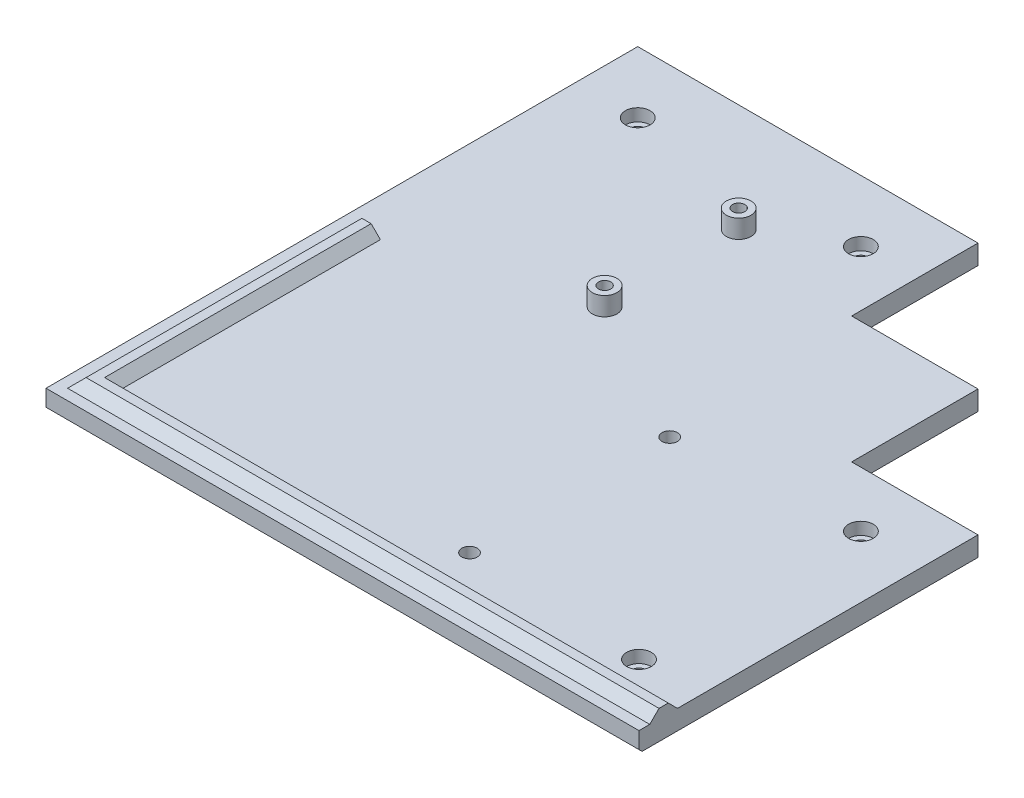
SolidWorks part; units mm, degrees
ref_plane "Front Plane" through (0, 0, 0) normal (0, 0, 1) x (1, 0, 0)
ref_plane "Top Plane" through (0, 0, 0) normal (0, 1, 0) x (1, 0, 0)
ref_plane "Right Plane" through (0, 0, 0) normal (1, 0, 0) x (0, 0, -1)
sketch "Sketch1" plane through (0, 0, 0) normal (0, 1, 0) x (1, 0, 0)
  line L1 (-96.2, 96) -> (96.2, 96)
  line L2 (-96.2, 96) -> (-96.2, -96)
  line L3 (-96.2, -96) -> (96.2, -96)
  line L4 (96.2, 96) -> (96.2, -96)
  line L5 (-96.2, 96) -> (96.2, -96) construction
  line L6 (-96.2, -96) -> (96.2, 96) construction
  point P0 (0, 0)
  dimension "D1" = 192
  dimension "D2" = 192.4
extrude "Boss-Extrude1" add sketch "Sketch1" along normal blind 6.35
sketch "Sketch2" plane through (0, 6.35, 0) normal (0, 1, 0) x (1, 0, 0)
  line L1 (-96.2, 96) -> (-55.2, 96)
  line L2 (-96.2, 96) -> (-96.2, 55)
  line L3 (-96.2, 55) -> (-55.2, 55) construction
  line L4 (-55.2, 96) -> (-55.2, 55) construction
  line L5 (-96.2, 55) -> (-55.2, 55)
  line L6 (-96.2, 55) -> (-96.2, 14)
  line L7 (-96.2, 14) -> (-55.2, 14)
  line L8 (-55.2, 55) -> (-55.2, 14)
  line L9 (-55.2, 96) -> (-14.2, 96)
  line L10 (-55.2, 96) -> (-55.2, 55)
  line L11 (-55.2, 55) -> (-14.2, 55)
  line L12 (-14.2, 96) -> (-14.2, 55)
  line M14 (96.2, 96) -> (-96.2, 96)
  line M15 (-96.2, 96) -> (-96.2, -96)
  dimension "D1" = 41
extrude "Cut-Extrude1" cut sketch "Sketch2" against normal up to next contours L8 L5 L7 M15 | L10 L5 M14 M15 | L12 L10 L11 M14 region at (-75.7, 6.35, -75.5) region at (-34.7, 6.35, -75.5) region at (-75.7, 6.35, -34.5)
sketch "Sketch3" plane through (0, 6.35, 0) normal (0, 1, 0) x (1, 0, 0)
  line L0 (-96.2, 76) -> (96.2, 76) construction
  line L1 (-96.2, 96) -> (-56.2, 96) construction
  line L2 (-96.2, 96) -> (-96.2, -96) construction
  line L3 (-96.2, -96) -> (-56.2, -96) construction
  line L4 (96.2, 96) -> (-96.2, 96)
  line L5 (96.2, -96) -> (96.2, 96)
  line L6 (-96.2, -96) -> (96.2, -96)
  line L7 (-96.2, 96) -> (-96.2, -96)
  line L8 (96.2, 96) -> (-96.2, 96) construction
  line L9 (96.2, -96) -> (96.2, 96) construction
  line L10 (-96.2, -96) -> (96.2, -96) construction
  line L11 (-96.2, 96) -> (-96.2, -96) construction
  line L12 (-56.2, 96) -> (-56.2, -96) construction
  line L13 (-96.2, 96) -> (96.2, 96) construction
  line L14 (-96.2, 96) -> (-96.2, 56) construction
  line L15 (-96.2, 56) -> (96.2, 56) construction
  line L16 (96.2, 96) -> (96.2, 56) construction
  line L17 (-76.2, 96) -> (-76.2, -96) construction
  point P20 (-76.2, -4)
  point P22 (-76.2, -76)
  point P24 (3.8, 76)
  point P26 (76.2, 76)
  dimension "D2" = 40
  dimension "D3" = 40
  dimension "D4" = 20
  dimension "D5" = 60
  dimension "D6" = 60
  dimension "D7" = 20
  dimension "D8" = 20
  dimension "D1" = 0
hole_wizard "CBORE for M4 SHCS1" positions "Sketch3" profile "Sketch4" counterbore size "M4" standard "ANSI Metric" end condition up to next
sketch "Sketch4" plane through (76.2, 6.35, -76) normal (1, 0, 0) x (0, 0, 1)
  line L0 (0, 0) -> (0, 6.35)
  line L1 (0, 6.35) -> (2.25, 6.35)
  line L3 (2.25, 6.35) -> (2.25, 4)
  line L4 (2.25, 4) -> (4, 4)
  line L5 (4, 4) -> (4, 0)
  line L7 (4, 0) -> (0, 0)
  line L11 (0, -6.35) -> (0, 107.95) construction
  dimension "Thru Hole Dia." = 4.5
  dimension "Thru Hole Depth" = 6.35
  dimension "C'Bore Dia." = 8
  dimension "C'Bore Depth" = 4
mirror "Mirror1" [suppressed] of bodies 105
delete or keep bodies "Body-Delete/Keep 1" [suppressed] type delete bodies bodies 105
mirror "Mirror2" [suppressed] of bodies 108
delete or keep bodies "Body-Delete/Keep 2" [suppressed] type delete bodies bodies 108
sketch "Sketch5" plane through (0, 6.35, 0) normal (0, 1, 0) x (1, 0, 0)
  line L0 (-18.7, -8.525) -> (-18.7, -73.475) construction
  line L1 (-56.2, -4.375) -> (18.8, -4.375) construction
  line L2 (-56.2, -4.375) -> (-56.2, -77.625) construction
  line L3 (-56.2, -77.625) -> (18.8, -77.625) construction
  line L4 (18.8, -4.375) -> (18.8, -77.625) construction
  line L5 (-96.2, -41) -> (96.2, -41) construction
  line L6 (-96.2, 14) -> (-96.2, -96) construction
  line L7 (96.2, -96) -> (96.2, 96) construction
  line L8 (-56.2, -41) -> (18.8, -41) construction
  circle A0 centre (-18.7, -8.525) radius 2.5
  circle A1 centre (-18.7, -73.475) radius 2.5
  point P12 (-18.7, -41)
  point P15 (-18.7, -41)
  dimension "D4" = 5
  dimension "D1" = 73.25
  dimension "D2" = 75
  dimension "D3" = 40
  dimension "D5" = 64.95
extrude "Cut-Extrude2" cut sketch "Sketch5" against normal blind 6
sketch "Sketch6" plane through (0, 0.35, 0) normal (0, 1, 0) x (1, 0, 0)
  circle A0 centre (-18.7, -8.525) radius 2.25
  circle A1 centre (-18.7, -73.475) radius 2.25
  dimension "D1" = 4.5
extrude "Cut-Extrude3" cut sketch "Sketch6" against normal up to next
sketch "Sketch7" plane through (0, 6.35, 0) normal (0, 1, 0) x (1, 0, 0)
  line L0 (96.2, -96) -> (96.2, 96) construction
  line L1 (28.45, 61) -> (163.95, 61) construction
  line L2 (28.45, 61) -> (28.45, 17.5) construction
  line L3 (28.45, 17.5) -> (163.95, 17.5) construction
  line L4 (163.95, 61) -> (163.95, 17.5) construction
  line L5 (28.45, 61) -> (163.95, 17.5) construction
  line L6 (28.45, 17.5) -> (163.95, 61) construction
  line L7 (96.2, 96) -> (-14.2, 96) construction
  circle A0 centre (28.45, 61) radius 1.75
  circle A1 centre (28.45, 17.5) radius 1.75
  point P0 (96.2, 39.25)
  dimension "D4" = 3.5
  dimension "D1" = 43.5
  dimension "D2" = 135.5
  dimension "D3" = 35
extrude "Cut-Extrude4" cut sketch "Sketch7" against normal up to next
sketch "Sketch11" plane through (0, 6.35, 0) normal (0, 1, 0) x (1, 0, 0)
  circle A0 centre (28.45, 17.5) radius 1.75 construction
  circle A1 centre (28.45, 61) radius 1.75 construction
  circle A2 centre (28.45, 17.5) radius 1.75
  circle A3 centre (28.45, 61) radius 1.75
  circle A4 centre (28.45, 61) radius 4
  circle A5 centre (28.45, 17.5) radius 4
  dimension "D1" = 8
extrude "Boss-Extrude2" add sketch "Sketch11" along normal blind 6
sketch "Sketch8" plane through (0, 12.35, 0) normal (0, 1, 0) x (1, 0, 0)
  circle A0 centre (28.45, 61) radius 2
  circle A1 centre (28.45, 17.5) radius 2
  dimension "D1" = 4
extrude "Cut-Extrude5" cut sketch "Sketch8" against normal blind 5
sketch "Sketch9" plane through (0, 6.35, 0) normal (0, 1, 0) x (1, 0, 0)
  line L2 (0, 0) -> (96.2, 0) construction
  line L3 (96.2, -96) -> (96.2, 96) construction
  line L4 (-96.2, -88) -> (88.2, -88)
  line L5 (88.2, -88) -> (88.2, 96)
  line L6 (-96.2, -88) -> (88.2, -88)
  line L7 (88.2, -88) -> (88.2, 0)
  dimension "D1" = 8
extrude "Extrude-Thin1" add sketch "Sketch9" along normal blind 3 thin thin type mid plane wall 3
chamfer "Chamfer1" distance 3 angle 45 4 edges at (-4.75, 6.35, 86.5) (86.7, 6.35, 43.25) (-3.25, 6.35, 89.5) (89.7, 6.35, 44.75)
chamfer "Chamfer2" distance 1 angle 45 2 edges at (0, 0, 96) (96.2, 0, 0)
mirror "Mirror3" about plane through (96.2, 6.35, -96) normal (-1, 0, 0) of bodies 115 113
delete or keep bodies "Body-Delete/Keep 4" type delete bodies bodies 115
equation "\"D2@Sketch1\"=384.8/2"
